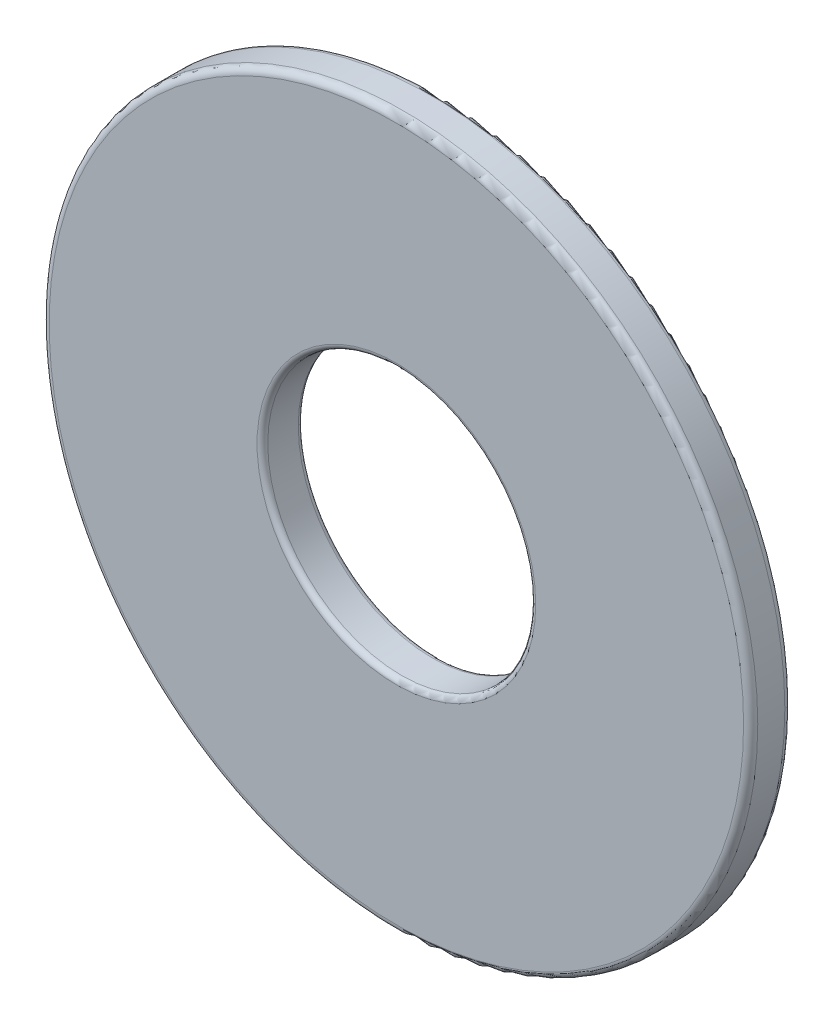
SolidWorks part; units mm, degrees
note: '?' marks a value the reader was unsure of.
other "Imported1" parameters "D1"=0.1321, "ID"=2.2, "OD"=5
ref_plane "Front Plane" through (0, 0, 0) normal (0, 0, 1) x (1, 0, 0)
ref_plane "Top Plane" through (0, 0, 0) normal (0, 1, 0) x (1, 0, 0)
ref_plane "Right Plane" through (0, 0, 0) normal (1, 0, 0) x (0, 0, -1)
sketch "Sketch1" plane through (0, 0, 0) normal (0, 0, 1) x (1, 0, 0)
  line L0 (-8.7312, 0) -> (8.7312, 0) construction
  line L1 (-3.302, 0) -> (3.302, 0) construction
  circle A0 centre (0, 0) radius 3.302 construction
  circle A1 centre (0, 0) radius 8.7312 construction
  point P8 (0, 0)
  point P9 (0, 8.7312)
  point P11 (3.302, 0)
  dimension "OD" = 17.4625
  dimension "ID" = 6.604
sketch "Sketch2" plane through (0, 0, 0) normal (1, 0, 0) x (0, 0, -1)
  line L0 (-0.508, 8.7312) -> (0.508, 8.7312) construction
  point P2 (0, 8.7312)
  dimension "Thickness" = 1.016
sketch "Sketch3" plane through (0, 0, 0) normal (0, 0, 1) x (1, 0, 0)
  circle A0 centre (0, 0) radius 3.302
  circle A1 centre (0, 0) radius 8.7312
extrude "Boss-Extrude1" add sketch "Sketch3" along normal up to vertex (0.508 mm away) and the other way up to vertex (0.508 mm away) up to point (0, 8.7312, 0.508) other way up to point (0, 8.7312, -0.508)
fillet "Fillet1" radius 0.1321 2 edges at (3.302, 0, 0.508) (3.302, 0, -0.508)
fillet "Fillet2" radius 0.1746 2 edges at (8.7312, 0, -0.508) (8.7312, 0, 0.508)
ref_axis "Center Axis 1" through (0, 0, 0.3759) along (0, 0, -1)?
equation "\"D1@Fillet1\"=\"ID@Sketch1\"*.02"
equation "\"D1@Fillet2\"=\"OD@Sketch1\"*.01"
